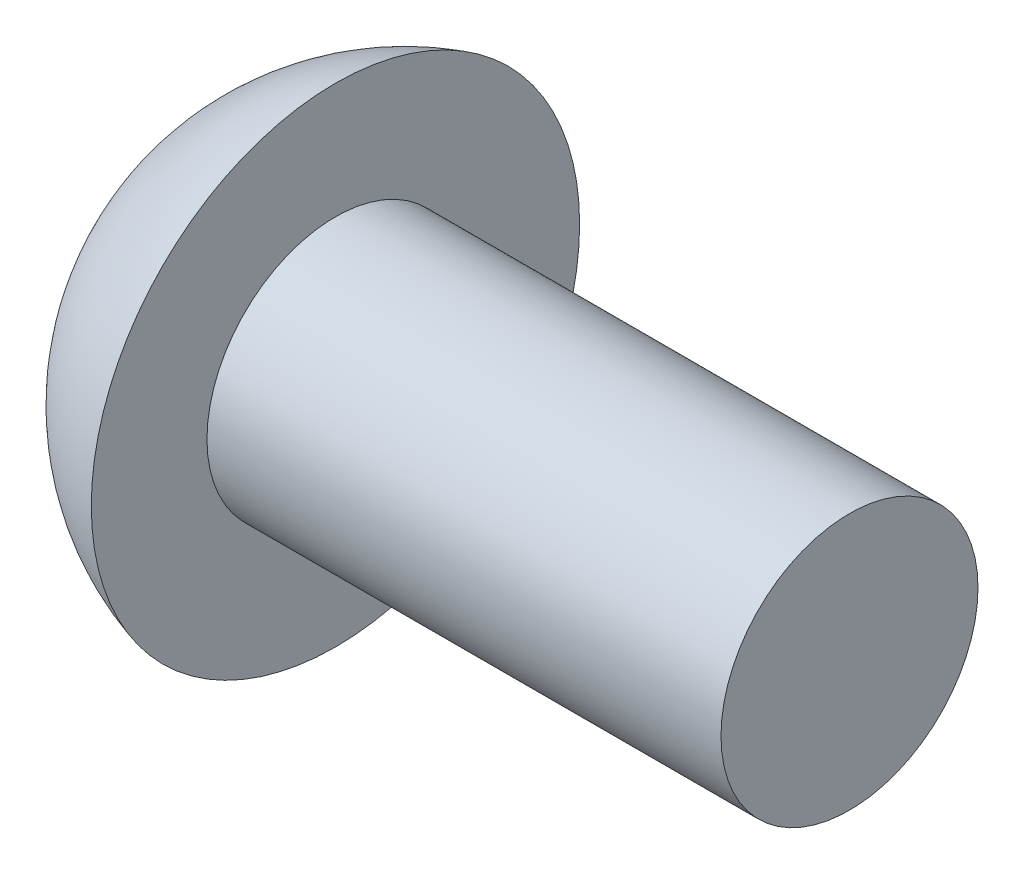
SolidWorks part; units mm, degrees
ref_plane "Front" through (0, 0, 0) normal (0, 0, 1) x (1, 0, 0)
ref_plane "Top" through (0, 0, 0) normal (0, 1, 0) x (1, 0, 0)
ref_plane "Right" through (0, 0, 0) normal (1, 0, 0) x (0, 0, -1)
sketch "Sketch1" plane through (0, 0, 0) normal (1, 0, 0) x (0, 0, -1)
  line L0 (0, 0) -> (1, 0) construction
  circle A0 centre (0, 0) radius 2.85
extrude "BaseHead" add sketch "Sketch1" along normal blind 1.65
sketch "Sketch2" plane through (1.65, 0, 0) normal (1, 0, 0) x (0, 0, -1)
  circle A0 centre (0, 0) radius 1.5
extrude "BaseBody" add sketch "Sketch2" along normal blind 6
cosmetic thread "ThreadCosmetic1" [suppressed] parameters "D1"=5, "THD_MINOR"=2.459
fillet "HeadFillet" [suppressed] radius 0.1
sketch "Sketch3" plane through (-13.4796, 2.4796, 0) normal (0, 0, 1) x (0, -1, 0)
  line L0 (2.4796, 13.4796) -> (2.4796, 41.0387) construction
  line L3 (-0.3704, 13.4796) -> (2.4796, 13.4796) construction
  line L5 (-5.3704, 15.1296) -> (-5.3704, 8.4796)
  line L6 (0.8296, 13.4796) -> (0.8296, 8.4796)
  line L7 (0.8296, 8.4796) -> (-5.3704, 8.4796)
  line L8 (-5.3704, 15.1296) -> (-0.3704, 15.1296)
  line L9 (-0.3704, 13.4796) -> (5.3296, 13.4796) construction
  arc A0 (-0.3704, 15.1296) -> (0.8296, 13.4796) centre (2.4796, 15.9409) ccw
  dimension "D2" = 5
  dimension "e" = 3.3
  dimension "D3" = 5
revolve "Cut-Revolve1" cut sketch "Sketch3" angle 360 about L0
sketch "Sketch4" plane through (0, 0, 0) normal (1, 0, 0) x (0, 0, -1)
  line L1 (1.1547, 0) -> (0.5774, 1)
  line L2 (0.5774, 1) -> (-0.5774, 1)
  line L3 (-0.5774, 1) -> (-1.1547, 0)
  line L4 (-1.1547, 0) -> (-0.5774, -1)
  line L5 (-0.5774, -1) -> (0.5774, -1)
  line L6 (0.5774, -1) -> (1.1547, 0)
  circle A0 centre (0, 0) radius 1 construction
  dimension "s" = 2
extrude "HexagonSocket" cut sketch "Sketch4" along normal blind 1.04
sketch "Sketch5" plane through (1.04, 0, 0) normal (-1, 0, 0) x (0, 0, 1)
  line L0 (0.5774, -1) -> (-0.5774, -1) construction
  line L1 (-0.5774, -1) -> (-1.1547, 0) construction
  line L2 (1.1547, 0) -> (0.5774, -1) construction
  line L3 (0.5774, 1) -> (1.1547, 0) construction
  line L4 (-1.1547, 0) -> (-0.5774, 1) construction
  line L5 (-0.5774, 1) -> (0.5774, 1) construction
  line L6 (0.5774, -1) -> (-0.5774, -1)
  line L7 (-0.5774, -1) -> (-1.1547, 0)
  line L8 (1.1547, 0) -> (0.5774, -1)
  line L9 (0.5774, 1) -> (1.1547, 0)
  line L10 (-1.1547, 0) -> (-0.5774, 1)
  line L11 (-0.5774, 1) -> (0.5774, 1)
extrude "Cut-Extrude2" cut sketch "Sketch5" against normal blind 5 draft 60
sketch "Sketch6" plane through (0, 0, 0) normal (0, 0, 1) x (1, 0, 0)
  line L0 (7.65, 1.2657) -> (7.7853, 1.5)
  line L1 (7.7853, 1.5) -> (7.7853, 1.7705)
  line L2 (7.7853, 1.7705) -> (7.5148, 1.7705)
  line L3 (7.5148, 1.7705) -> (7.5148, 1.5)
  line L4 (7.5148, 1.5) -> (7.65, 1.2657)
  line L5 (0, 0) -> (24.7294, 0) construction
  line L6 (7.65, -1.5) -> (7.65, 1.5) construction
  dimension "D1" = 0.2705
  dimension "D2" = 3
revolve "Cut-Revolve10" [suppressed] cut sketch "Sketch6" angle 360 about L5
pattern_linear "LPattern10" [suppressed] count 16 spacing 0.3246 along (-1, 0, 0) of bodies 106
equation "\"D1@ThreadCosmetic1\" = \"l@BaseBody\" - \"a@Sketch1\""
equation "\"D2@Sketch6\" = \"d@Sketch2\""
equation "\"D1@Sketch6\" =  (\"d@Sketch2\" - \"THD_MINOR@ThreadCosmetic1\" )  / 2"
equation "\"D3@LPattern10\" = \"D1@Sketch6\" * 1.2"
equation "\"D1@LPattern10\" = \"D1@ThreadCosmetic1\" / \"D3@LPattern10\" + 1"
